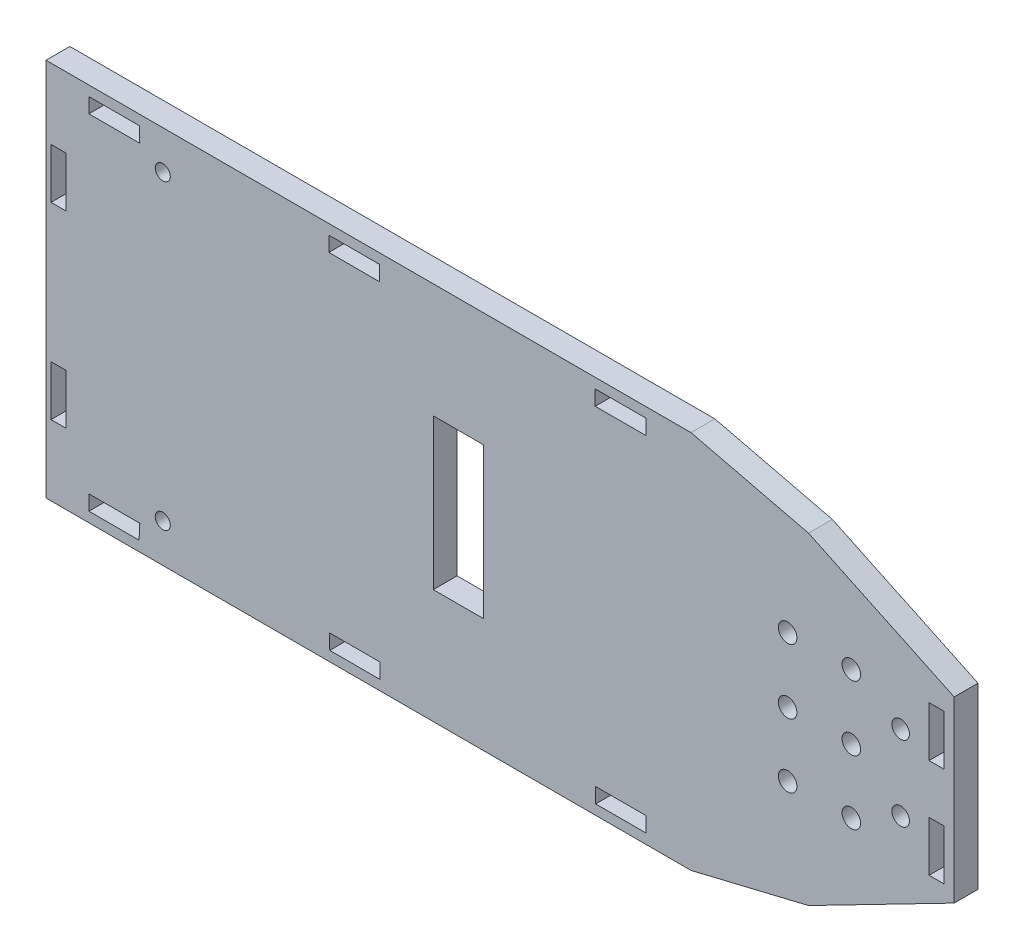
SolidWorks part; units mm, degrees
ref_plane "Front Plane" through (0, 0, 0) normal (0, 0, 1) x (1, 0, 0)
ref_plane "Top Plane" through (0, 0, 0) normal (0, 1, 0) x (1, 0, 0)
ref_plane "Right Plane" through (0, 0, 0) normal (1, 0, 0) x (0, 0, -1)
sketch "Sketch1" plane through (0, 0, 0) normal (0, 0, 1) x (1, 0, 0)
  line L1 (-90.5, -37.785) -> (90.5, -37.785)
  line L2 (-90.5, -37.785) -> (-90.5, 37.785)
  line L3 (-90.5, 37.785) -> (90.5, 37.785)
  line L4 (90.5, -37.785) -> (90.5, 37.785)
  line L5 (-90.5, -37.785) -> (90.5, 37.785) construction
  line L6 (-90.5, 37.785) -> (90.5, -37.785) construction
  point P0 (0, 0)
extrude "Boss-Extrude2" add sketch "Sketch1" along normal blind 4.75
sketch "Sketch6" plane through (0, 0, 4.75) normal (0, 0, 1) x (1, 0, 0)
  line L0 (-90.5, 0) -> (90.5, 0) construction
  line L1 (-90.5, 37.785) -> (-90.5, -37.785) construction
  line L2 (90.5, -37.785) -> (90.5, 37.785) construction
  line L3 (0, 37.785) -> (0, -37.785) construction
  line L4 (90.5, 37.785) -> (-90.5, 37.785) construction
  line L5 (-90.5, -37.785) -> (90.5, -37.785) construction
  line L10 (-17.18, 37.785) -> (-17.18, -37.785) construction
  line L11 (-81.9552, 32.802) -> (-71.8128, 32.7986)
  line L12 (-89.5, 23.75) -> (-86.5, 23.75)
  line L13 (-89.5, 23.75) -> (-89.5, 13.75)
  line L14 (-89.5, 13.75) -> (-86.5, 13.75)
  line L15 (-86.5, 23.75) -> (-86.5, 13.75)
  line L16 (-89.5, -13.75) -> (-86.5, -13.75)
  line L17 (-89.5, -13.75) -> (-89.5, -23.75)
  line L18 (-89.5, -23.75) -> (-86.5, -23.75)
  line L19 (-86.5, -13.75) -> (-86.5, -23.75)
  line L20 (-34.1308, 32.7983) -> (-34.1388, 35.785)
  line L21 (-34.1308, 32.7983) -> (-24.043, 32.7816)
  line L22 (-34.1388, 35.785) -> (-24.043, 35.785)
  line L23 (-24.043, 32.7816) -> (-24.043, 35.785)
  line L24 (-71.8128, 32.7986) -> (-71.8594, 35.785)
  line L25 (-81.9552, 32.802) -> (-81.9552, 35.785)
  line L26 (-81.9552, 35.785) -> (-71.8594, 35.785)
  line L27 (-81.9552, -32.785) -> (-71.8128, -32.7884)
  line L28 (-71.9552, -35.785) -> (-71.8128, -32.7884)
  line L29 (-81.9552, -35.785) -> (-71.9552, -35.785)
  line L30 (-81.9552, -35.785) -> (-81.9552, -32.785)
  line L31 (-33.9472, -35.801) -> (-23.9472, -35.8088)
  line L32 (-33.9472, -35.801) -> (-33.9552, -32.801)
  line L33 (-23.9472, -35.8088) -> (-23.9469, -32.8043)
  line L34 (-33.9552, -32.801) -> (-23.9469, -32.8043)
  line L35 (85.5, 14.9) -> (85.5, 4.9)
  line L36 (88.5, 14.9) -> (88.5, 4.9)
  line L37 (85.5, 4.9) -> (88.5, 4.9)
  line L38 (85.5, 14.9) -> (88.5, 14.9)
  line L39 (88.5, 9.9) -> (85.5, 9.9) construction
  line L40 (29.0528, 32.7816) -> (29.0528, 35.785)
  line L41 (18.957, 32.7816) -> (29.0528, 32.7816)
  line L42 (18.957, 32.7816) -> (18.957, 35.785)
  line L43 (18.957, 35.785) -> (29.0528, 35.785)
  line L44 (19.0531, -32.8054) -> (29.0528, -32.8063)
  line L45 (19.0528, -35.8054) -> (19.0531, -32.8054)
  line L46 (19.0528, -35.8054) -> (29.0528, -35.8063)
  line L47 (29.0528, -35.8063) -> (29.0528, -32.8063)
  line L50 (-67.23, -30.095) -> (79.8334, -30.095) construction
  line L51 (-13.3116, 15) -> (-3.3116, 15)
  line L52 (-13.3116, 15) -> (-13.3116, -15)
  line L53 (-13.3116, -15) -> (-3.3116, -15)
  line L54 (-3.3116, 15) -> (-3.3116, -15)
  line L59 (85.5, -14.9) -> (88.5, -14.9)
  line L64 (85.5, -4.9) -> (85.5, -14.9)
  line L65 (85.5, -4.9) -> (88.5, -4.9)
  line L66 (88.5, -4.9) -> (88.5, -14.9)
  line L67 (38.0552, -37.785) -> (61.4663, -32.14)
  line L68 (61.4663, -32.14) -> (90.5, -17.2)
  line L69 (38.0552, 37.785) -> (61.4663, 32.14)
  line L70 (61.4663, 32.14) -> (90.5, 18.3856)
  line L71 (79.8334, -30.095) -> (79.8334, -36.495)
  circle A2 centre (-67.23, 30.095) radius 1.5
  circle A3 centre (-67.23, -30.095) radius 1.5
  circle A12 centre (70.0065, -12.7534) radius 1.85
  circle A13 centre (70.0065, 12.8925) radius 1.85
  circle A14 centre (70.0065, 0) radius 1.85
  circle A15 centre (57.3065, 12.8925) radius 1.85
  circle A16 centre (57.3065, 0) radius 1.85
  circle A17 centre (57.3065, -12.7534) radius 1.85
  circle A20 centre (79.8334, -7.5) radius 1.75
  circle A21 centre (79.8334, 7.5) radius 1.75
  point P21 (90.5, 0)
  line M4 (90.5, -37.785) -> (90.5, 37.785)
  line M5 (90.5, 37.785) -> (-90.5, 37.785)
  line M7 (-90.5, -37.785) -> (90.5, -37.785)
  dimension "D1" = 43
  dimension "D3" = 27.5
  dimension "D2" = 43
  dimension "D4" = 15
  dimension "D6" = 2
  dimension "D5" = 7.5
  dimension "D7" = 2
  dimension "D8" = 2
  dimension "D9" = 2
  dimension "D10" = 1
  dimension "D11" = 13.75
  dimension "D12" = 10
extrude "Cut-Extrude7" cut sketch "Sketch6" against normal blind 9 contours L38 L35 L37 L36 | A14 | A12 | A17 | A16 | A15 | L43 L42 L41 L40 | L54 L51 L52 L53 | L46 L47 L44 L45 | L21 L23 L22 L20 | L26 L25 L11 L24 | A2 | L15 L12 L13 L14 | L19 L16 L17 L18 | L30 L29 L28 L27 | A3 | L34 L32 L31 L33 | L68 L67 M7 M4 | L69 L70 M4 M5 | A21 | L66 L65 L64 L59 | A20 | A13 | A21 | L59 L66 L65 L64 region at (-76.8947, 34.2915, 4.75) region at (-88, 18.75, 4.75) region at (-88, -18.75, 4.75) region at (-29.0842, 34.2877, 4.75) region at (-76.9204, -34.2823, 4.75) region at (-28.9479, -34.3036, 4.75) region at (87, 9.9, 4.75) region at (24.0049, 34.2833, 4.75) region at (24.0529, -34.3058, 4.75) region at (-8.3116, 0, 4.75) region at (87, -9.9, 4.75) region at (74.7992, 31.6648, 4.75) region at (75.0311, -31.3147, 4.75) region at (-67.23, 30.095, 4.75) region at (-67.23, -30.095, 4.75) region at (70.0065, -12.7534, 4.75) region at (70.0065, 12.8925, 4.75) region at (70.0065, 0, 4.75) region at (57.3065, 12.8925, 4.75) region at (57.3065, 0, 4.75) region at (57.3065, -12.7534, 4.75) region at (79.8334, -7.5, 4.75) region at (79.8334, 7.5, 4.75)
